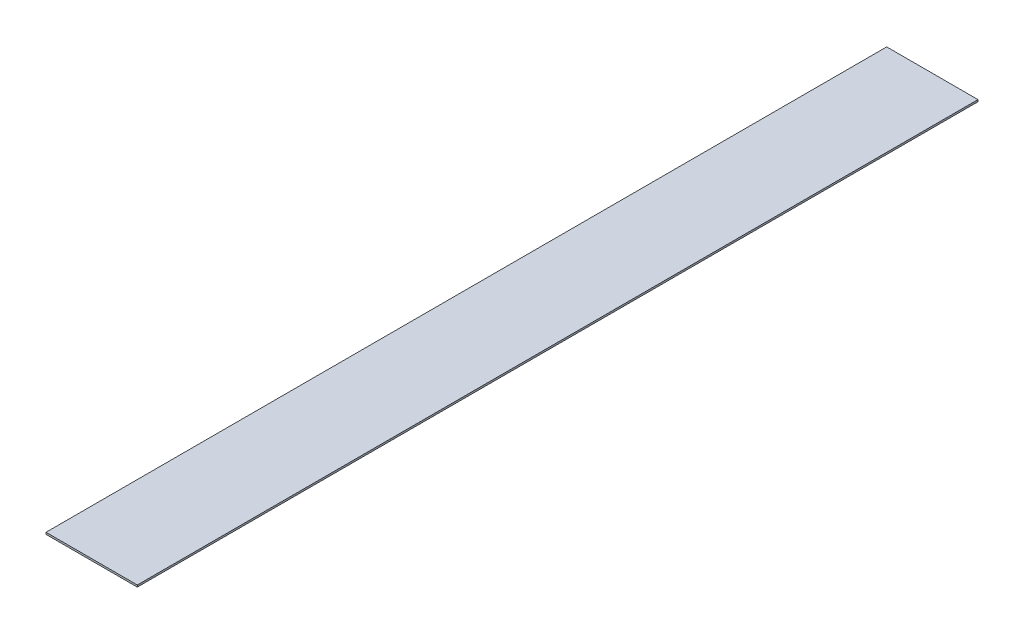
SolidWorks part; units mm, degrees
ref_plane "Front Plane" through (0, 0, 0) normal (0, 0, 1) x (1, 0, 0)
ref_plane "Top Plane" through (0, 0, 0) normal (0, 1, 0) x (1, 0, 0)
ref_plane "Right Plane" through (0, 0, 0) normal (1, 0, 0) x (0, 0, -1)
sketch "Sketch2" plane through (0, 0, 0) normal (0, 1, 0) x (1, 0, 0)
  line L0 (2.46, -22.65) -> (2.46, 22.65)
  line L1 (-2.46, -22.65) -> (-2.46, 22.65)
  line L2 (2.46, -22.65) -> (-2.46, -22.65)
  line L3 (2.46, 22.65) -> (-2.46, 22.65)
  line L4 (2.46, 22.65) -> (-2.46, -22.65) construction
  line L5 (-2.46, 22.65) -> (2.46, -22.65) construction
  point P2 (0, -22.65)
  point P5 (0, 22.65)
  point P6 (0, 0)
  dimension "D1" = 45.3
  dimension "D2" = 4.92
extrude "Boss-Extrude1" add sketch "Sketch2" along normal mid plane 0.1
